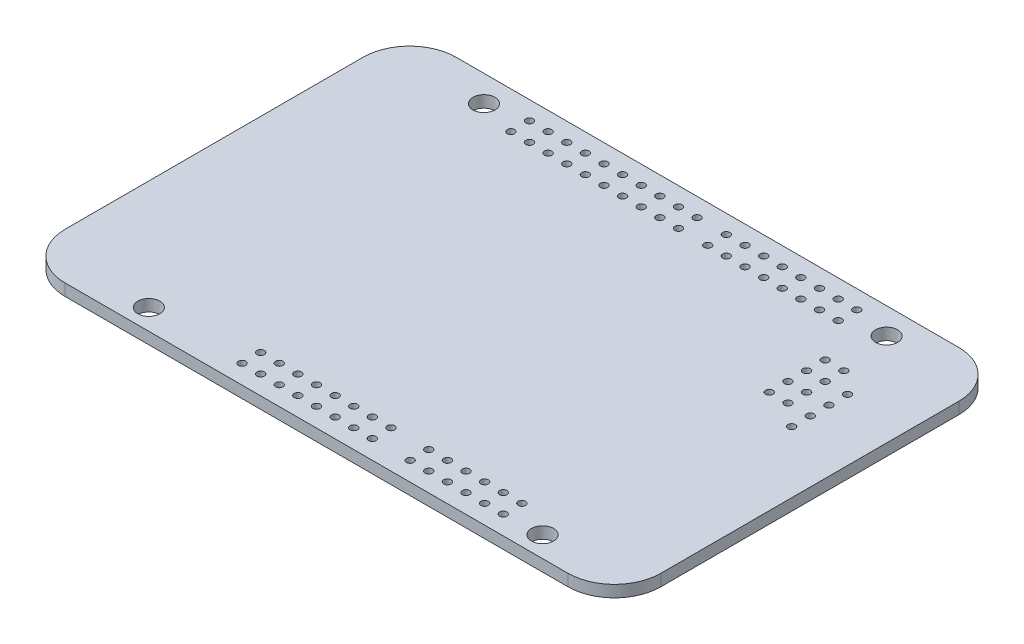
SolidWorks part; units mm, degrees
ref_plane "Front Plane" through (0, 0, 0) normal (0, 0, 1) x (1, 0, 0)
ref_plane "Top Plane" through (0, 0, 0) normal (0, 1, 0) x (1, 0, 0)
ref_plane "Right Plane" through (0, 0, 0) normal (1, 0, 0) x (0, 0, -1)
sketch "Sketch1" plane through (0, 0, 0) normal (0, 1, 0) x (1, 0, 0)
  line L1 (0, 0) -> (81.28, 0)
  line L2 (0, 0) -> (0, 53.34)
  line L3 (0, 53.34) -> (81.28, 53.34)
  line L4 (81.28, 0) -> (81.28, 53.34)
  dimension "D1" = 53.34
  dimension "D2" = 81.28
extrude "Boss-Extrude1" add sketch "Sketch1" along normal blind 1.6
fillet "Fillet1" radius 6.35 4 edges at (0, 0.8, -53.34) (81.28, 0.8, -53.34) (81.28, 0.8, 0) (0, 0.8, 0)
sketch "Sketch2" plane through (0, 1.6, 0) normal (0, 1, 0) x (1, 0, 0)
  line L0 (0, 46.99) -> (0, 6.35) construction
  line L1 (6.35, 0) -> (74.93, 0) construction
  line L2 (14.9479, 2.8194) -> (14.9479, 53.34) construction
  line L3 (74.93, 53.34) -> (6.35, 53.34) construction
  line L4 (14.9479, 2.8194) -> (84.3994, 2.8194) construction
  circle A0 centre (14.9479, 2.8194) radius 1.5
  circle A1 centre (13.7287, 49.7586) radius 1.5
  circle A2 centre (68.6562, 49.7586) radius 1.5
  circle A3 centre (68.6562, 2.8194) radius 1.5
  circle A4 centre (27.9019, 2.5781) radius 0.5
  circle A5 centre (50.8381, 2.5781) radius 0.5
  circle A6 centre (18.8722, 48.2854) radius 0.5
  circle A7 centre (45.7327, 48.2854) radius 0.5
  circle A8 centre (67.2922, 35.1257) radius 0.5
  circle A9 centre (72.8802, 40.2057) radius 0.5
  dimension "D3" = 3
  dimension "D4" = 1
  dimension "D1" = 14.9479
  dimension "D2" = 2.8194
  dimension "D5" = 0.2413
  dimension "D6" = 12.954
  dimension "D7" = 35.8902
  dimension "D8" = 53.7083
  dimension "D9" = 52.3443
  dimension "D10" = 32.3063
  dimension "D11" = 57.9323
  dimension "D12" = 37.3863
  dimension "D13" = 46.9392
  dimension "D14" = 1.2192
  dimension "D15" = 3.9243
  dimension "D16" = 45.466
  dimension "D17" = 30.7848
  dimension "D18" = 53.7083
  dimension "D19" = 46.9392
extrude "Cut-Extrude1" cut sketch "Sketch2" against normal up to next
pattern_linear "LPattern1" count 8 spacing 2.54 along (1, 0, 0) count 2 spacing 2.54 along (0, 0, -1) of face at (27.9019, 0, -3.0781)
pattern_linear "LPattern2" count 6 spacing 2.54 along (1, 0, 0) count 2 spacing 2.54 along (0, 0, -1) of face at (50.8381, 0, -3.0781)
pattern_linear "LPattern3" count 10 spacing 2.54 along (1, 0, 0) count 2 spacing 2.54 along (0, 0, -1) of face at (18.8722, 0, -48.7854)
pattern_linear "LPattern4" count 8 spacing 2.54 along (1, 0, 0) count 2 spacing 2.54 along (0, 0, -1) of face at (45.7327, 0, -48.7854)
pattern_linear "LPattern5" count 4 spacing 2.54 along (0, 0, -1) count 2 spacing 2.54 along (1, 0, 0) of face at (67.2922, 0, -35.6257)
pattern_linear "LPattern6" count 4 spacing 2.54 along (0, 0, 1) of face at (72.8802, 0, -40.7057)
